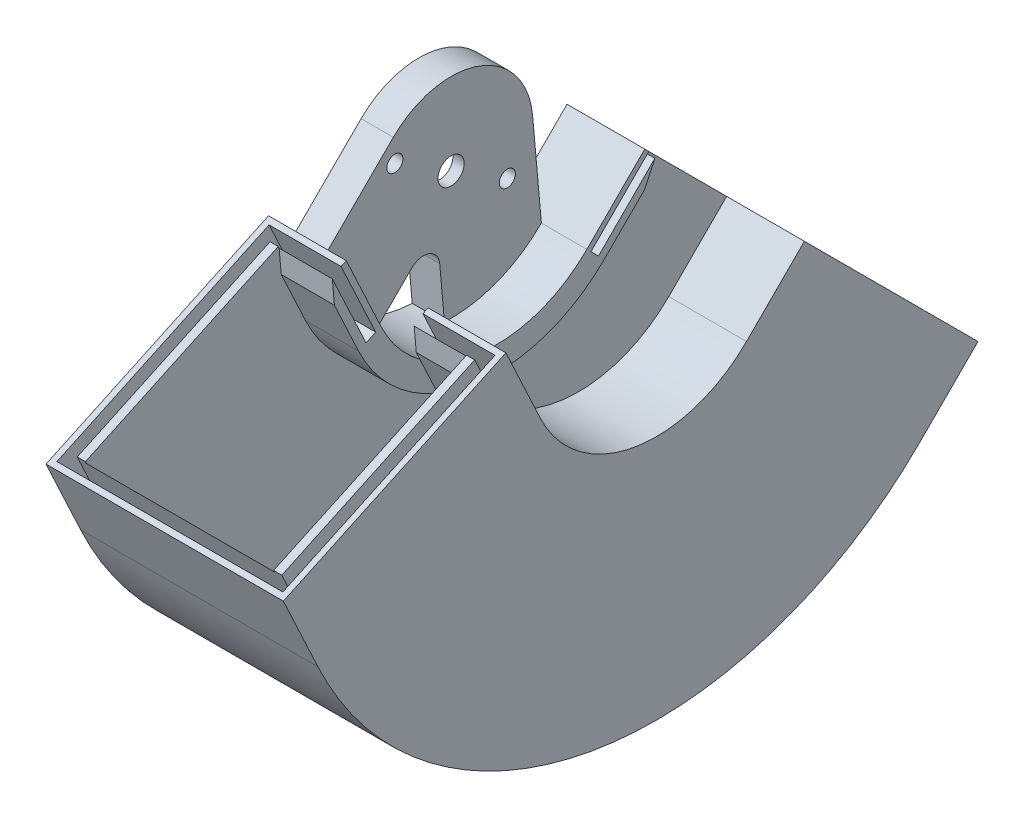
SolidWorks part; units mm, degrees
ref_plane "Front Plane" through (0, 0, 0) normal (0, 0, 1) x (1, 0, 0)
ref_plane "Top Plane" through (0, 0, 0) normal (0, 1, 0) x (1, 0, 0)
ref_plane "Right Plane" through (0, 0, 0) normal (1, 0, 0) x (0, 0, -1)
sketch "Sketch3" plane through (0, 0, 0) normal (1, 0, 0) x (0, 0, -1)
  line L0 (-35.9115, -16.7458) -> (-98.0661, -45.729)
  line L1 (28.0184, -28.0184) -> (76.5118, -76.5118)
  line L2 (-35.9115, -16.7458) -> (0, 0) construction
  line L3 (0, 0) -> (28.0184, -28.0184) construction
  line L4 (0, 40.513) -> (0, -40.513) construction
  line L5 (-98.0661, -45.729) -> (-104.9722, -48.9493)
  line L6 (76.5118, -76.5118) -> (81.8999, -81.8999)
  arc A2 (-98.0661, -45.729) -> (76.5118, -76.5118) centre (0, 0) ccw
  arc A4 (-42.8176, -19.9662) -> (33.4066, -33.4066) centre (0, 0) ccw
  arc A5 (-35.9115, -16.7458) -> (28.0184, -28.0184) centre (0, 0) ccw
  arc A6 (-104.9722, -48.9493) -> (81.8999, -81.8999) centre (0, 0) ccw
  dimension "D1" = 216.408
  dimension "D2" = 135
  dimension "D3" = 94.488
  dimension "D4" = 7.62
  dimension "D6" = 7.62
  dimension "D5" = 110
extrude "Boss-Extrude2" add sketch "Sketch3" along normal blind 58.42 contours L5 A6 L6 A2 | A5 L0 A4 L1 region at (0, -39.8305, 7.0232) region at (0, -108.5257, 19.136)
sketch "Sketch4" plane through (58.42, 0, 0) normal (1, 0, 0) x (0, 0, -1)
  line L0 (-104.9722, -48.9493) -> (-35.9115, -16.7458)
  line L1 (28.0184, -28.0184) -> (81.8999, -81.8999)
  arc A0 (-35.9115, -16.7458) -> (28.0184, -28.0184) centre (0, 0) ccw
  arc A1 (-35.9115, -16.7458) -> (28.0184, -28.0184) centre (0, 0) ccw construction
  arc A2 (-104.9722, -48.9493) -> (81.8999, -81.8999) centre (0, 0) ccw
  arc A3 (-104.9722, -48.9493) -> (81.8999, -81.8999) centre (0, 0) ccw construction
  arc M1 (28.0184, -28.0184) -> (-35.9115, -16.7458) centre (0, 0) cw
  line M2 (-35.9115, -16.7458) -> (-42.8176, -19.9662)
  arc M3 (-42.8176, -19.9662) -> (33.4066, -33.4066) centre (0, 0) ccw
  line M4 (33.4066, -33.4066) -> (28.0184, -28.0184)
extrude "Boss-Extrude3" add sketch "Sketch4" along normal blind 7.62 contours L0 A2 L1 M3 | M4 M1 M2 M3 region at (58.42, -72.5593, 12.7942) region at (58.42, -19.1001, 39.0176)
ref_plane "Midplane" through (29.21, 0, 0) normal (-1, 0, 0) x (0, 0, 1)
mirror "Mirror1" about plane through (29.21, 0, 0) normal (-1, 0, 0) of "Boss-Extrude3"
sketch "Sketch6" plane through (0, 0, 0) normal (0, 0.9063, 0.4226) x (1, 0, 0)
  line L27 (-5.842, -41.402) -> (64.262, -41.402)
  line L28 (-5.842, -41.402) -> (-5.842, -114.046)
  line L29 (-5.842, -114.046) -> (64.262, -114.046)
  line L30 (64.262, -41.402) -> (64.262, -114.046)
  line L31 (-2.54, -44.704) -> (60.96, -44.704)
  line L32 (-2.54, -44.704) -> (-2.54, -110.744)
  line L33 (-2.54, -110.744) -> (60.96, -110.744)
  line L34 (60.96, -44.704) -> (60.96, -110.744)
  line L35 (58.42, -47.244) -> (0, -47.244) construction
  line L36 (0, -108.204) -> (0, 37.0079) construction
  line L37 (58.42, 37.0079) -> (58.42, -108.204) construction
  line L38 (58.42, -108.204) -> (0, -108.204) construction
  line L40 (0, -47.244) -> (58.42, -47.244)
  line L41 (0, -47.244) -> (0, -108.204)
  line L42 (0, -108.204) -> (58.42, -108.204)
  line L43 (58.42, -47.244) -> (58.42, -108.204)
  line L44 (-7.62, -39.624) -> (66.04, -39.624)
  line L45 (-7.62, -39.624) -> (-7.62, -115.824)
  line L46 (-7.62, -115.824) -> (66.04, -115.824)
  line L47 (66.04, -39.624) -> (66.04, -115.824)
  line M21 (-7.62, -39.624) -> (-7.62, -115.824)
  line M22 (-7.62, -115.824) -> (66.04, -115.824)
  line M23 (66.04, -115.824) -> (66.04, -39.624)
  line M24 (66.04, -39.624) -> (-7.62, -39.624)
  line M25 (58.42, -108.204) -> (0, -108.204)
  line M26 (0, -108.204) -> (0, -47.244)
  line M27 (0, -47.244) -> (58.42, -47.244)
  line M28 (58.42, -47.244) -> (58.42, -108.204)
  dimension "D1" = 3.302
  dimension "D2" = 3.302
  dimension "D3" = 3.302
  dimension "D4" = 3.302
  dimension "D5" = 2.54
  dimension "D6" = 2.54
  dimension "D7" = 2.54
  dimension "D8" = 2.54
extrude "Boss-Extrude4" add sketch "Sketch6" along normal blind 25.4 contours L27 L30 L29 L28 M24 M21 M22 M23 | L34 L31 L32 L33 M28 M25 M26 M27 region at (29.21, -19.2799, 41.3459) region at (29.21, -17.1937, 36.8721)
sketch "Sketch7" plane through (0, 0, 0) normal (0, 0.7071, -0.7071) x (1, 0, 0)
  line L0 (-5.842, 114.046) -> (64.262, 114.046)
  line L1 (-5.842, 114.046) -> (-5.842, 41.402)
  line L2 (-5.842, 41.402) -> (64.262, 41.402)
  line L3 (64.262, 114.046) -> (64.262, 41.402)
  line L4 (-2.54, 110.744) -> (60.96, 110.744)
  line L5 (-2.54, 110.744) -> (-2.54, 44.704)
  line L6 (-2.54, 44.704) -> (60.96, 44.704)
  line L7 (60.96, 110.744) -> (60.96, 44.704)
  line L8 (0, 108.204) -> (58.42, 108.204)
  line L9 (0, 108.204) -> (0, 47.244)
  line L10 (0, 47.244) -> (58.42, 47.244)
  line L11 (58.42, 108.204) -> (58.42, 47.244)
  line L12 (-7.62, 115.824) -> (66.04, 115.824)
  line L13 (-7.62, 115.824) -> (-7.62, 39.624)
  line L14 (-7.62, 39.624) -> (66.04, 39.624)
  line L15 (66.04, 115.824) -> (66.04, 39.624)
  line L16 (58.42, 108.204) -> (0, 108.204) construction
  line L17 (58.42, 47.244) -> (58.42, 108.204) construction
  line L18 (66.04, 115.824) -> (-7.62, 115.824) construction
  line L19 (66.04, 39.624) -> (66.04, 115.824) construction
  line L20 (-7.62, 39.624) -> (-7.62, 115.824) construction
  line L21 (66.04, 39.624) -> (-7.62, 39.624) construction
  line M17 (66.04, 115.824) -> (-7.62, 115.824)
  line M18 (-7.62, 115.824) -> (-7.62, 39.624)
  line M19 (-7.62, 39.624) -> (66.04, 39.624)
  line M20 (66.04, 39.624) -> (66.04, 115.824)
  line M21 (0, 47.244) -> (0, 108.204)
  line M22 (0, 108.204) -> (58.42, 108.204)
  line M23 (58.42, 108.204) -> (58.42, 47.244)
  line M24 (58.42, 47.244) -> (0, 47.244)
  dimension "D1" = 3.302
  dimension "D2" = 3.302
  dimension "D3" = 3.302
  dimension "D4" = 3.302
  dimension "D5" = 2.54
  dimension "D6" = 2.54
  dimension "D7" = 2.54
  dimension "D8" = 2.54
extrude "Boss-Extrude5" add sketch "Sketch7" along normal blind 25.4 contours L0 L3 L2 L1 M20 M17 M18 M19 | L7 L4 L5 L6 M24 M21 M22 M23 region at (29.21, -77.66, -77.66) region at (29.21, -81.1505, -81.1505)
chamfer "Chamfer1" distance 7.62 angle 20 4 edges at (29.21, -22.7088, 108.8006) (29.21, 3.054, 53.5521) (29.21, -58.5513, -94.4723) (29.21, -15.446, -51.3671) first distance on face at (29.21, -34.2189, 103.4334) first distance on face at (29.21, -8.4561, 48.1849) first distance on face at (29.21, -67.5315, -85.492) first distance on face at (29.21, -24.4263, -42.3868)
ref_plane "Plane2" through (0, -1.8917, 0.3336) normal (0, -0.9848, 0.1736) x (-1, 0, 0)
sketch "Sketch10" plane through (0, -1.8917, 0.3336) normal (0, -0.9848, 0.1736) x (-1, 0, 0)
  line L0 (-66.04, 109.4463) -> (7.62, 109.4463) construction
  line L1 (-16.51, 95.5358) -> (-41.91, 95.5358)
  line L2 (-16.51, 95.5358) -> (-16.51, -82.1857)
  line L3 (-16.51, -82.1857) -> (-41.91, -82.1857)
  line L4 (-41.91, 95.5358) -> (-41.91, -82.1857)
  point P4 (-29.21, 109.4463)
  point P5 (-29.21, 95.5358)
  dimension "D1" = 25.4
extrude "Cut-Extrude3" cut sketch "Sketch10" along normal up to next
sketch "Sketch11" plane through (-7.62, 0, 0) normal (-1, 0, 0) x (0, 0, 1)
  line L0 (-25.2982, 2.2719) -> (-28.0184, -28.0184)
  line L4 (3.5302, -23.1342) -> (2.0542, -39.5707)
  line L5 (12.1726, -19.9871) -> (23.8722, -31.6256)
  line L6 (-17.454, -10.7521) -> (17.454, 10.7521) construction
  line L7 (17.9134, 18.0075) -> (41.2788, -5.2357)
  line L8 (46.646, 6.2744) -> (35.9115, -16.7458) construction
  line L10 (6.8516, -18.8153) -> (-8.6912, 23.8668) construction
  line L11 (35.9115, -16.7458) -> (46.646, 6.2744)
  line L12 (35.9115, -16.7458) -> (41.2788, -5.2357)
  arc A1 (-28.0184, -28.0184) -> (35.9115, -16.7458) centre (0, 0) ccw construction
  circle A3 centre (0, 0) radius 4.064
  arc A4 (17.9134, 18.0075) -> (-25.2982, 2.2719) centre (0, 0) ccw
  circle A6 centre (-17.454, -10.7521) radius 2.5
  circle A7 centre (17.454, 10.7521) radius 2.5
  arc A8 (3.5302, -23.1342) -> (12.1726, -19.9871) centre (8.5899, -23.5886) cw
  arc A11 (23.8722, -31.6256) -> (35.9115, -16.7458) centre (0, 0) ccw
  arc A12 (-28.0184, -28.0184) -> (35.9115, -16.7458) centre (0, 0) ccw
  arc A13 (-28.0184, -28.0184) -> (2.0542, -39.5707) centre (0, 0) ccw
  point P22 (0, 0)
  dimension "D3" = 8.128
  dimension "D2" = 25.4
  dimension "D1" = 5
  dimension "D5" = 5.08
  dimension "D4" = 41
  dimension "D6" = 0
extrude "Boss-Extrude6" add sketch "Sketch11" against normal blind 10
sketch "Sketch12" plane through (-7.62, 0, 0) normal (-1, 0, 0) x (0, 0, 1)
  circle A0 centre (0, 0) radius 17
  dimension "D1" = 34
extrude "Cut-Extrude4" cut sketch "Sketch12" against normal blind 6.5
